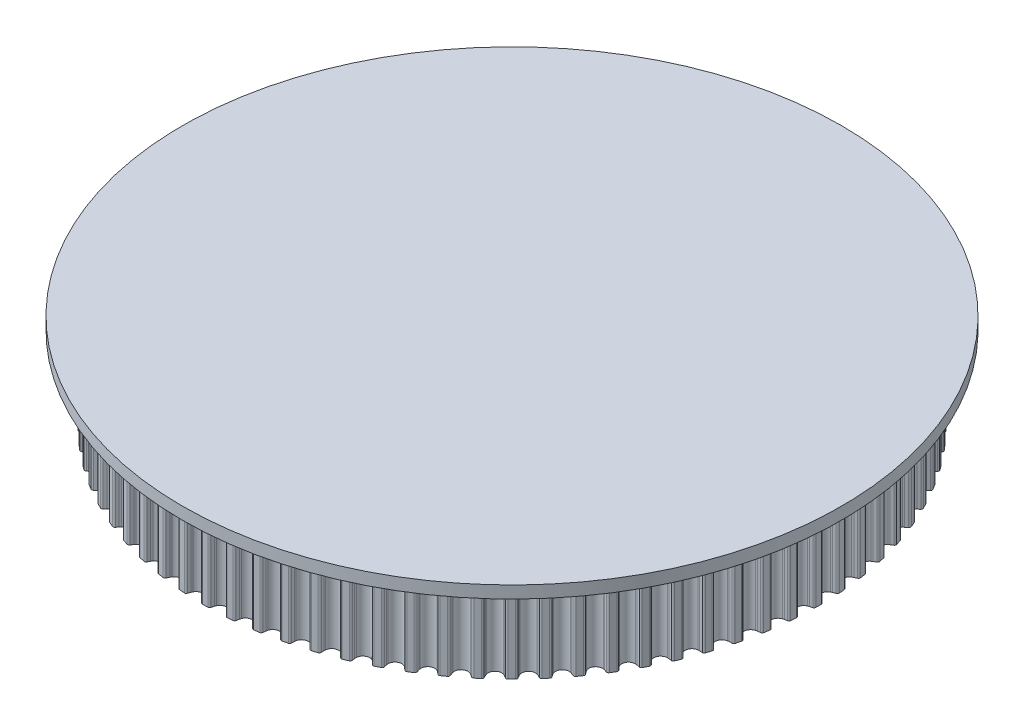
SolidWorks part; units mm, degrees
other "标注1"
sketch "草图3" plane through (-18.85, 0, 18.85) normal (-0.2707, -0.9304, 0.2473) x (-0.8697, 0.1263, -0.4772)
ref_plane "前视基准面" through (0, 0, 0) normal (0, 0, 1) x (1, 0, 0)
ref_plane "上视基准面" through (0, 0, 0) normal (0, 1, 0) x (1, 0, 0)
ref_plane "右视基准面" through (0, 0, 0) normal (1, 0, 0) x (0, 0, -1)
sketch "草图1" plane through (0, 0, 0) normal (0, 1, 0) x (1, 0, 0)
  line L0 (0, 0) -> (0, 23.6319) construction
  line L1 (0, 25.135) -> (1.9984, 25.0554) construction
  line L2 (0.9992, 25.0952) -> (0, 0) construction
  line L3 (0, 25.135) -> (0.2436, 25.1253) construction
  line L4 (0.438, 24.8022) -> (0.379, 25.0227)
  line L5 (0, 0) -> (1.8829, 23.607) construction
  line L6 (1.9984, 25.0554) -> (2.1275, 26.6736)
  line L7 (0.9694, 24.3458) -> (0.9915, 24.9004) construction
  line L8 (0.9992, 25.0952) -> (1.0093, 25.349) construction
  line L10 (0.9992, 25.0952) -> (1.3989, 25.0793) construction
  line L12 (1.0093, 25.349) -> (1.409, 25.3331) construction
  line L13 (1.409, 25.3331) -> (1.3989, 25.0793) construction
  line L14 (1.5353, 24.7585) -> (1.6117, 24.9736)
  line L15 (1.9984, 25.0554) -> (1.7548, 25.0651) construction
  line L16 (2.1275, 26.6736) -> (0, 26.7104)
  line L17 (0, 26.7104) -> (0, 25.135)
  circle A0 centre (0, 0) radius 25.135 construction
  arc A4 (1.4803, 24.6375) -> (0.4833, 24.6772) centre (0.9915, 24.9004) cw
  arc A5 (1.5353, 24.7585) -> (1.4803, 24.6375) centre (0.5995, 25.1111) cw
  arc A10 (1.7636, 25.0731) -> (1.9984, 25.0554) centre (0, 0) cw
  arc A11 (1.7636, 25.0731) -> (1.6117, 24.9736) centre (1.7531, 24.9234) ccw
  arc A12 (0.438, 24.8022) -> (0.4833, 24.6772) centre (1.3989, 25.0793) ccw
  arc A13 (0.2355, 25.1339) -> (0.379, 25.0227) centre (0.2341, 24.9839) cw
  arc A14 (0.2355, 25.1339) -> (0, 25.135) centre (0, 0) ccw
  dimension "D3" = 0.555
  dimension "D5" = 15
  dimension "D6" = 1
  dimension "D9" = 50.27
  dimension "D7" = 0.15
  dimension "D1" = 2
  dimension "D2" = 0.195
  dimension "D4" = 0.4
  dimension "D8" = 0.254
  dimension "D10" = 0.2283
sketch "草图2" plane through (0, 0, 0) normal (0, 1, 0) x (1, 0, 0)
  circle A0 centre (0, 0) radius 25.135
  dimension "D1" = 50.27
extrude "凸台-拉伸1" add sketch "草图2" along normal blind 7
extrude "切除-拉伸1" cut sketch "草图1" along normal blind 7
pattern_circular "阵列(圆周)1" count 80 over 360 about axis through (0, 7, 0) along (0, -1, 0) of "切除-拉伸1" reverse direction yes
sketch "草图4" plane through (0, 7, 0) normal (0, 1, 0) x (1, 0, 0)
  circle A0 centre (0, 0) radius 27
  dimension "D1" = 54
extrude "凸台-拉伸2" add sketch "草图4" along normal blind 1
